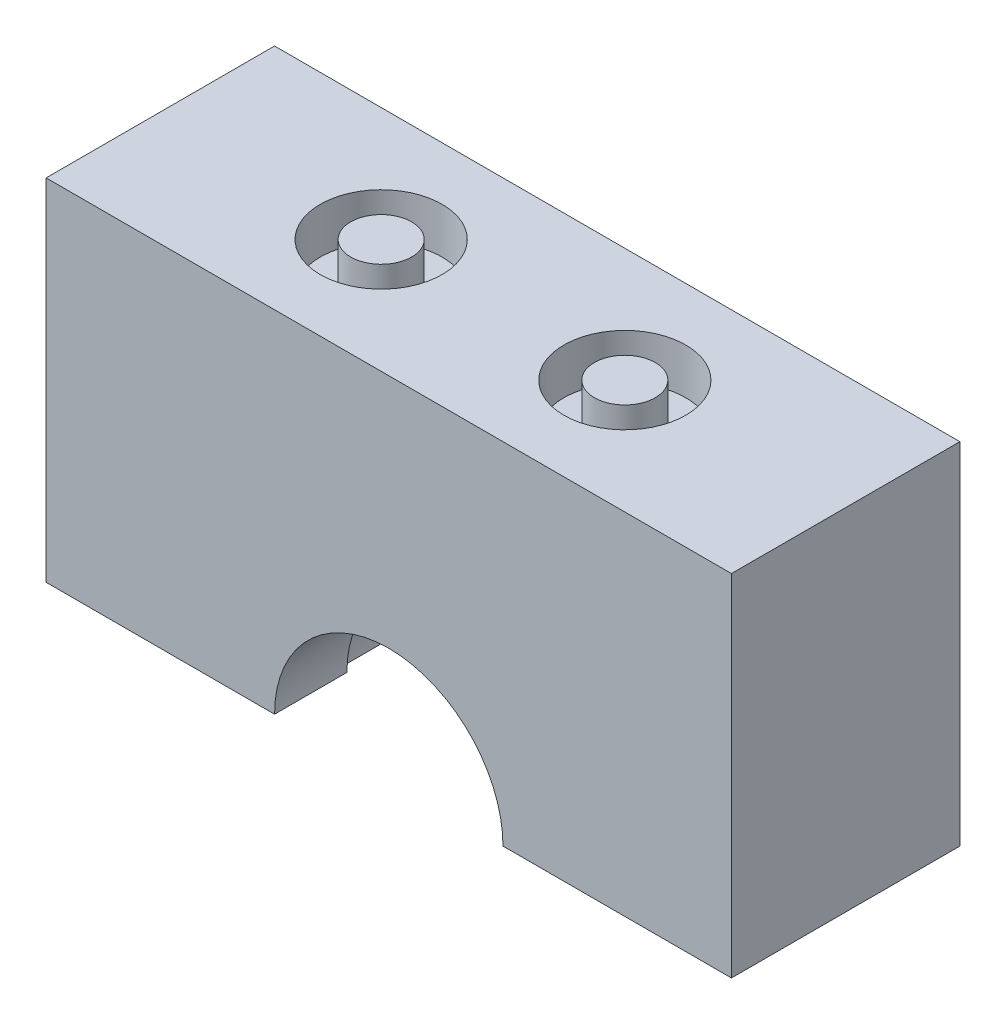
SolidWorks part; units mm, degrees
ref_plane "Front Plane" through (0, 0, 0) normal (0, 0, 1) x (1, 0, 0)
ref_plane "Top Plane" through (0, 0, 0) normal (0, 1, 0) x (1, 0, 0)
ref_plane "Right Plane" through (0, 0, 0) normal (1, 0, 0) x (0, 0, -1)
sketch "Sketch1" plane through (0, 0, 0) normal (0, 0, 1) x (1, 0, 0)
  line L0 (-22.5, 0) -> (-22.5, 23)
  line L1 (-22.5, 23) -> (22.5, 23)
  line L2 (22.5, 23) -> (22.5, 0)
  line L3 (-22.5, 0) -> (-7.5, 0)
  line L4 (22.5, 0) -> (7.5, 0)
  arc A0 (7.5, 0) -> (-7.5, 0) centre (0, 0) ccw
  dimension "D1" = 15
  dimension "D2" = 45
  dimension "D3" = 23
extrude "Boss-Extrude1" add sketch "Sketch1" along normal blind 15 contours L2 L1 L0 | L4 L3 A0 region at (0, 12.2763, 0)
sketch "Sketch2" plane through (0, 0, 0) normal (1, 0, 0) x (0, 0, -1)
  line L0 (0, 0) -> (-27.3188, 0) construction
  line L2 (-4.75, 6.4825) -> (-10.25, 6.4825)
  line L3 (-4.75, 6.4825) -> (-4.75, 8)
  line L4 (-4.75, 8) -> (-10.25, 8)
  line L5 (-10.25, 6.4825) -> (-10.25, 8)
  line L6 (-15, 23) -> (0, 23) construction
  point P11 (-7.5, 23)
  point P12 (-7.5, 8)
  dimension "D1" = 8
  dimension "D2" = 5.5
revolve "Cut-Revolve2" cut sketch "Sketch2" angle 360 about L0
sketch "Sketch3" plane through (0, 23, 0) normal (0, 1, 0) x (1, 0, 0)
  line L0 (-22.5, -7.5) -> (22.5, -7.5) construction
  line L1 (-22.5, -15) -> (-22.5, 0) construction
  line L2 (22.5, -15) -> (22.5, 0) construction
  line L3 (-22.5, 0) -> (22.5, 0) construction
  circle A0 centre (-8, -7.5) radius 2
  circle A1 centre (8, -7.5) radius 2
  circle A2 centre (-8, -7.5) radius 4
  circle A3 centre (8, -7.5) radius 4
  point P12 (0, 0)
  dimension "D1" = 4
  dimension "D4" = 8
  dimension "D2" = 8
  dimension "D3" = 8
extrude "Cut-Extrude1" cut sketch "Sketch3" against normal blind 3
